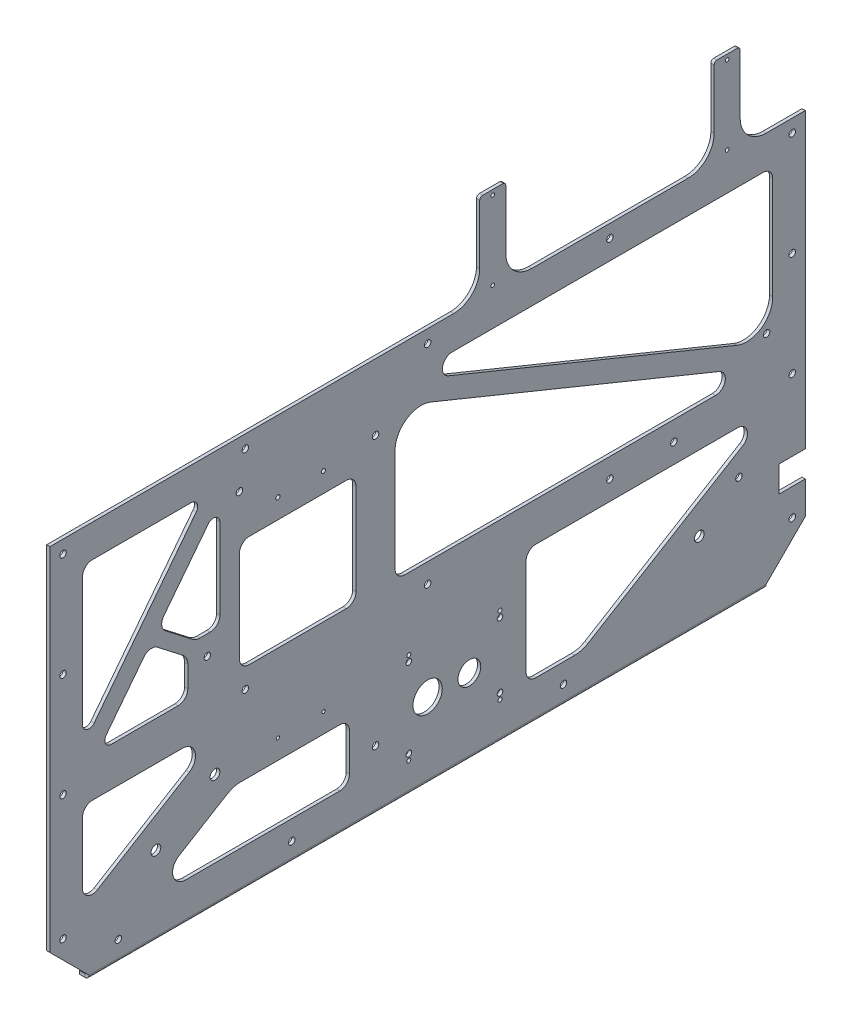
SolidWorks part; units mm, degrees
note: The reader was unsure of these and kept them because the rebuilt part matched: flange length of "Edge-Flange1".
material "6061-T6 (SS)"
ref_plane "Front Plane" through (0, 0, 0) normal (0, 0, 1) x (1, 0, 0)
ref_plane "Top Plane" through (0, 0, 0) normal (0, 1, 0) x (1, 0, 0)
ref_plane "Right Plane" through (0, 0, 0) normal (1, 0, 0) x (0, 0, -1)
sketch "Sketch1" plane through (0, 0, 0) normal (1, 0, 0) x (0, 0, -1)
  line L0 (330.2, 0) -> (-330.2, 0)
  line L1 (-330.2, 0) -> (-368.3, 38.1)
  line L2 (-368.3, 38.1) -> (-368.3, 381)
  line L3 (-368.3, 381) -> (368.3, 381)
  line L4 (368.3, 381) -> (368.3, 38.1)
  line L5 (368.3, 38.1) -> (330.2, 0)
  point P4 (0, 0)
  dimension "D1" = 736.6
  dimension "D2" = 381
  dimension "D3" = 38.1
  dimension "D4" = 45
base flange "Base-Flange1" sketch "Sketch1" thickness 3.175 reverse thickness direction no parameters "D1"=0.7366
sketch "Sketch11" plane through (0, 0, 0) normal (1, 0, 0) x (0, 0, -1)
  line L0 (304.8, 381) -> (304.8, 466.725)
  line L1 (304.8, 466.725) -> (279.4, 466.725)
  line L2 (279.4, 466.725) -> (279.4, 381)
  line L3 (368.3, 381) -> (-368.3, 381) construction
  line L4 (279.4, 381) -> (304.8, 381)
  line L5 (368.3, 381) -> (-368.3, 381) construction
  line L6 (368.3, 38.1) -> (368.3, 381) construction
  line L8 (76.2, 381) -> (50.8, 381)
  line L9 (76.2, 381) -> (76.2, 466.725)
  line L10 (76.2, 466.725) -> (50.8, 466.725)
  line L11 (50.8, 381) -> (50.8, 466.725)
  dimension "D1" = 25.4
  dimension "D2" = 85.725
  dimension "D3" = 63.5
  dimension "D4" = 228.6
base flange "Tab1" sketch "Sketch11" thickness 3.175 reverse thickness direction no parameters "D1"=0.7366
sketch "Sketch6" plane through (0, 0, 0) normal (1, 0, 0) x (0, 0, -1)
  circle A0 centre (264.9792, 73.025) radius 4.7625
  circle A1 centre (0, 69.85) radius 14.2875
  circle A2 centre (-264.9792, 73.025) radius 4.7625
  circle A3 centre (132.4896, 14.2875) radius 3.175 construction
  circle A4 centre (-132.4896, 14.2875) radius 3.175 construction
  circle A5 centre (132.4896, 14.2875) radius 3.175
  circle A6 centre (-132.4896, 14.2875) radius 3.175
  dimension "D1" = 28.575
  dimension "D2" = 9.525
  dimension "D3" = 9.525
extrude "Cut-Extrude1" cut sketch "Sketch6" against normal through all normal cut yes
sketch "Sketch7" plane through (0, 0, 0) normal (1, 0, 0) x (0, 0, -1)
  line L0 (368.3, 95.25) -> (368.3, 69.85)
  line L2 (368.3, 95.25) -> (342.9, 95.25)
  line L4 (368.3, 69.85) -> (342.9, 69.85)
  line L7 (342.9, 95.25) -> (342.9, 69.85)
  line L8 (349.2669, 95.25) -> (346.0496, 95.25) construction
  line L9 (342.9, 92.1004) -> (342.9, 88.8831) construction
  line L12 (279.4, 381) -> (76.2, 381) construction
  line L13 (-368.3, 381) -> (-368.3, 38.1) construction
  line L16 (-368.3, 368.3) -> (368.3, 368.3) construction
  line L17 (368.3, 38.1) -> (368.3, 381) construction
  line L18 (355.6, 368.3) -> (355.6, 165.1) construction
  line L19 (-355.6, 368.3) -> (-355.6, 165.1) construction
  circle A0 centre (-50.8, 53.975) radius 2.6035 construction
  circle A1 centre (-50.8, 53.975) radius 2.6035 construction
  circle A2 centre (-355.6, 43.3605) radius 3.175 construction
  circle A3 centre (-355.6, 165.1) radius 3.175 construction
  circle A4 centre (-177.8, 165.1) radius 3.175 construction
  circle A5 centre (0, 165.1) radius 3.175 construction
  circle A6 centre (177.8, 165.1) radius 3.175 construction
  circle A7 centre (355.6, 43.3605) radius 3.175 construction
  circle A8 centre (355.6, 165.1) radius 3.175 construction
  circle A9 centre (-355.6, 43.3605) radius 3.175
  circle A10 centre (-355.6, 165.1) radius 3.175
  circle A11 centre (-177.8, 165.1) radius 3.175
  circle A12 centre (0, 165.1) radius 3.175
  circle A13 centre (177.8, 165.1) radius 3.175
  circle A14 centre (355.6, 43.3605) radius 3.175
  circle A15 centre (355.6, 165.1) radius 3.175
  circle A16 centre (-146.05, 311.4675) radius 1.5875 construction
  circle A17 centre (-214.8334, 211.6192) radius 3.175
  circle A18 centre (-301.625, 15.875) radius 3.175 construction
  circle A19 centre (-301.625, 15.875) radius 3.175
  circle A20 centre (-146.05, 311.4675) radius 1.5875 construction
  circle A21 centre (-146.05, 311.4675) radius 2.032
  circle A22 centre (-101.6, 311.4675) radius 2.032
  circle A23 centre (-101.6, 311.4675) radius 1.5875 construction
  circle A24 centre (-101.6, 311.4675) radius 1.5875 construction
  circle A25 centre (303.625, 103.575) radius 3.175 construction
  circle A26 centre (240.125, 165.1) radius 3.175 construction
  circle A27 centre (330.6125, 211.525) radius 3.175 construction
  circle A28 centre (303.625, 103.575) radius 3.175
  circle A29 centre (-101.6, 108.2675) radius 1.5875 construction
  circle A30 centre (-146.05, 108.2675) radius 1.5875 construction
  circle A31 centre (-101.6, 108.2675) radius 1.5875
  circle A32 centre (-146.05, 108.2675) radius 1.5875
  circle A33 centre (-50.8, 316.23) radius 2.6035 construction
  circle A34 centre (-50.8, 316.23) radius 2.6035 construction
  circle A35 centre (240.125, 165.1) radius 3.175
  circle A36 centre (330.6125, 211.525) radius 3.175
  circle A47 centre (-355.6, 368.3) radius 3.175
  circle A48 centre (-177.8, 368.3) radius 3.175
  circle A49 centre (0, 368.3) radius 3.175
  circle A50 centre (177.8, 368.3) radius 3.175
  circle A51 centre (355.6, 368.3) radius 3.175
  circle A52 centre (-50.8, 316.23) radius 3.175
  circle A53 centre (-50.8, 53.975) radius 3.175
  circle A54 centre (-355.6, 266.7) radius 3.175
  circle A55 centre (355.6, 266.7) radius 3.175
  circle A56 centre (63.5, 461.9625) radius 1.3891 construction
  circle A57 centre (63.5, 385.7625) radius 1.3891 construction
  circle A58 centre (63.5, 461.9625) radius 1.3891 construction
  circle A59 centre (63.5, 385.7625) radius 1.3891 construction
  circle A60 centre (63.5, 461.9625) radius 1.7859
  circle A61 centre (63.5, 385.7625) radius 1.7859
  circle A62 centre (292.1, 461.9625) radius 1.3891 construction
  circle A63 centre (292.1, 385.7625) radius 1.3891 construction
  circle A64 centre (292.1, 461.9625) radius 1.3891 construction
  circle A65 centre (292.1, 385.7625) radius 1.3891 construction
  circle A66 centre (292.1, 461.9625) radius 1.7859
  circle A67 centre (292.1, 385.7625) radius 1.7859
  dimension "D6" = 6.35
  dimension "D7" = 4.064
  dimension "D2" = 6.35
  dimension "D11" = 6.35
  dimension "D12" = 6.35
  dimension "D13" = 3.5719
  dimension "D1" = 25.4
  dimension "D3" = 12.7
  dimension "D4" = 169.3808
  dimension "D5" = 153.4666
  dimension "D8" = 12.7
  dimension "D10" = 12.7
  dimension "D9" = 5
extrude "Cut-Extrude2" cut sketch "Sketch7" against normal through all normal cut yes
sketch "Sketch8" plane through (0, 0, 0) normal (1, 0, 0) x (0, 0, -1)
  circle A0 centre (70.5879, 38.1) radius 2.7261 construction
  circle A6 centre (-18.3121, 108.585) radius 2.7261 construction
  circle A7 centre (-18.3121, 31.115) radius 2.7261 construction
  circle A8 centre (70.5879, 38.1) radius 2.7261
  circle A9 centre (40.7162, 69.85) radius 11.1125 construction
  circle A10 centre (-18.3121, 108.585) radius 2.7261
  circle A11 centre (-18.3121, 31.115) radius 2.7261
  circle A12 centre (40.7162, 69.85) radius 11.1125
  circle A13 centre (70.5879, 101.6) radius 2.7261 construction
  circle A14 centre (70.5879, 101.6) radius 2.7261
  circle A15 centre (70.5879, 107.442) radius 1.9514 construction
  circle A16 centre (70.5879, 32.258) radius 1.9514 construction
  circle A17 centre (-18.3121, 25.273) radius 1.9514 construction
  circle A18 centre (-18.3121, 114.427) radius 1.9514 construction
  circle A19 centre (70.5879, 107.442) radius 1.9514
  circle A20 centre (70.5879, 32.258) radius 1.9514
  circle A21 centre (-18.3121, 25.273) radius 1.9514
  circle A22 centre (-18.3121, 114.427) radius 1.9514
extrude "Cut-Extrude3" cut sketch "Sketch8" against normal through all normal cut yes
sketch "Sketch9" plane through (0, 0, 0) normal (1, 0, 0) x (0, 0, -1)
  line L0 (-207.3469, 108.0375) -> (-232.6594, 28.575) construction
  line L1 (-493.8589, 28.575) -> (-213.6969, 28.575) construction
  line L2 (-493.8589, 28.575) -> (-493.8589, -31.75) construction
  line L3 (-493.8589, -31.75) -> (-213.6969, -31.75) construction
  line L4 (-213.6969, 28.575) -> (-213.6969, -31.75) construction
  line L5 (-410.4594, 28.575) -> (-207.3469, 108.0375) construction
  line L6 (-207.3469, 108.0375) -> (-286.8094, 133.35) construction
  line L7 (-347.1344, 388.112) -> (-286.8094, 388.112) construction
  line L8 (-347.1344, 388.112) -> (-347.1344, 107.95) construction
  line L9 (-347.1344, 107.95) -> (-286.8094, 107.95) construction
  line L10 (-286.8094, 388.112) -> (-286.8094, 107.95) construction
  line L11 (-286.8094, 311.15) -> (-207.3469, 108.0375) construction
  line L12 (-368.3, 299.4001) -> (-450.85, 299.4001) construction
  line L13 (-368.3, 381) -> (-368.3, 38.1) construction
  circle A0 centre (-207.3469, 108.0375) radius 4.7625
  circle A1 centre (0, 69.85) radius 101.6 construction
  circle A2 centre (-207.3469, 108.0375) radius 218.1031 construction
  point P8 (0, -31.75)
  point P22 (-425.45, 108.0375)
  dimension "D1" = 9.525
  dimension "D4" = 203.2
  dimension "D11" = 82.55
  dimension "D2" = 60.325
  dimension "D3" = 280.162
  dimension "D5" = 18.9625
  dimension "D6" = 177.8
  dimension "D7" = 139.7
  dimension "D8" = 25.4
  dimension "D9" = 177.8
  dimension "D10" = 6.35
  dimension "D12" = 25.4
extrude "Cut-Extrude4" cut sketch "Sketch9" against normal through all normal cut yes
sketch "Sketch10" plane through (0, 0, 0) normal (1, 0, 0) x (0, 0, -1)
  line L0 (-207.3469, 108.0375) -> (-183.5344, 84.225) construction
  line L1 (-207.3469, 108.0375) -> (-183.5344, 131.85) construction
  line L2 (-207.3469, 108.0375) -> (-312.821, 108.0375) construction
  line L3 (-207.3469, 108.0375) -> (-207.3469, 197.5591) construction
  circle A0 centre (-207.3469, 108.0375) radius 33.676 construction
  circle A1 centre (-183.5344, 335.05) radius 3.175
  dimension "D1" = 45
  dimension "D2" = 6.35
  dimension "D3" = 47.625
  dimension "D4" = 203.2
extrude "Cut-Extrude5" cut sketch "Sketch10" against normal through all normal cut yes
fillet "Fillet1" [suppressed] radius 1.5875
fillet "Fillet2" radius 2.794 4 edges at (-1.5875, 466.725, -279.4) (-1.5875, 466.725, -304.8) (-1.5875, 466.725, -76.2) (-1.5875, 466.725, -50.8)
fillet "Fillet3" radius 25.4 4 edges at (-1.5875, 381, -279.4) (-1.5875, 381, -76.2) (-1.5875, 381, -50.8) (-1.5875, 381, -304.8)
sketch "Sketch12" plane through (0, 0, 0) normal (1, 0, 0) x (0, 0, -1)
  line L0 (355.6, 165.1) -> (-355.6, 165.1) construction
  line L1 (23.9702, 349.25) -> (327.025, 349.25)
  line L2 (-79.375, 292.4175) -> (-174.0094, 292.4175)
  line L3 (336.55, 349.25) -> (336.55, 184.15) construction
  line L4 (336.55, 184.15) -> (-31.75, 184.15) construction
  line L5 (-31.75, 184.15) -> (-31.75, 349.25) construction
  line L6 (336.55, 339.725) -> (336.55, 239.5952)
  line L7 (-31.75, 349.25) -> (336.55, 349.25) construction
  line L8 (355.6, 368.3) -> (355.6, 165.1) construction
  line L9 (355.6, 368.3) -> (-355.6, 368.3) construction
  line L10 (-355.6, 368.3) -> (-355.6, 165.1) construction
  line L11 (280.8298, 184.15) -> (-22.225, 184.15)
  line L12 (-183.5344, 282.8925) -> (-183.5344, 193.675)
  line L13 (-69.85, 282.8925) -> (-69.85, 193.675)
  line L14 (-79.375, 184.15) -> (-174.0094, 184.15)
  line L15 (301.5471, 216.0804) -> (20.3691, 330.907)
  line L16 (3.2529, 317.3196) -> (284.4309, 202.493)
  line L17 (-31.75, 193.675) -> (-31.75, 293.8048)
  line L18 (329.3478, 184.15) -> (336.55, 201.7861) construction
  line L19 (-325.1809, 210.4894) -> (-225.5776, 339.0102)
  line L20 (-336.55, 349.25) -> (-202.5844, 349.25) construction
  line L21 (-336.55, 349.25) -> (-336.55, 184.15) construction
  line L22 (-336.55, 184.15) -> (-202.5844, 184.15) construction
  line L23 (-202.5844, 349.25) -> (-202.5844, 184.15) construction
  line L24 (-213.9535, 322.9106) -> (-257.34, 266.9278)
  line L25 (-230.5968, 349.25) -> (-327.025, 349.25)
  line L26 (-336.55, 339.725) -> (-336.55, 214.3792)
  line L27 (-202.5844, 319.0208) -> (-202.5844, 240.1942)
  line L28 (-212.1094, 230.6692) -> (-221.7586, 230.6692)
  line L29 (-233.8834, 214.4059) -> (-233.8834, 193.675)
  line L30 (-243.4084, 184.15) -> (-308.5376, 184.15)
  line L31 (-336.55, 195.8195) -> (-321.4926, 184.15) construction
  line L32 (-217.6418, 349.25) -> (-202.5844, 337.5805) construction
  line L33 (-238.8038, 224.4442) -> (-263.4257, 243.5261)
  line L34 (-229.5382, 233.3309) -> (-255.646, 253.5644)
  line L35 (-226.1038, 230.6692) -> (-233.8834, 220.6309) construction
  line L36 (-276.7891, 241.8321) -> (-313.5567, 194.3898)
  arc A0 (301.5471, 216.0804) -> (336.55, 239.5952) centre (311.15, 239.5952) ccw
  arc A1 (3.2529, 317.3196) -> (-31.75, 293.8048) centre (-6.35, 293.8048) ccw
  arc A2 (284.4309, 202.493) -> (280.8298, 184.15) centre (280.8298, 193.675) cw
  arc A3 (20.3691, 330.907) -> (23.9702, 349.25) centre (23.9702, 339.725) cw
  arc A4 (-255.646, 253.5644) -> (-257.34, 266.9278) centre (-249.8113, 261.0931) cw
  arc A5 (-263.4257, 243.5261) -> (-276.7891, 241.8321) centre (-269.2604, 235.9974) ccw
  arc A6 (-233.8834, 193.675) -> (-243.4084, 184.15) centre (-243.4084, 193.675) cw
  arc A7 (-202.5844, 240.1942) -> (-212.1094, 230.6692) centre (-212.1094, 240.1942) cw
  arc A8 (-327.025, 349.25) -> (-336.55, 339.725) centre (-327.025, 339.725) ccw
  arc A9 (327.025, 349.25) -> (336.55, 339.725) centre (327.025, 339.725) cw
  arc A10 (-22.225, 184.15) -> (-31.75, 193.675) centre (-22.225, 193.675) cw
  arc A11 (-183.5344, 193.675) -> (-174.0094, 184.15) centre (-174.0094, 193.675) ccw
  arc A12 (-69.85, 193.675) -> (-79.375, 184.15) centre (-79.375, 193.675) cw
  arc A13 (-69.85, 282.8925) -> (-79.375, 292.4175) centre (-79.375, 282.8925) ccw
  arc A14 (-174.0094, 292.4175) -> (-183.5344, 282.8925) centre (-174.0094, 282.8925) ccw
  arc A15 (-213.9535, 322.9106) -> (-202.5844, 319.0208) centre (-208.9344, 319.0208) cw
  arc A16 (-325.1809, 210.4894) -> (-336.55, 214.3792) centre (-330.2, 214.3792) cw
  arc A17 (-313.5567, 194.3898) -> (-308.5376, 184.15) centre (-308.5376, 190.5) ccw
  arc A18 (-225.5776, 339.0102) -> (-230.5968, 349.25) centre (-230.5968, 342.9) ccw
  arc A19 (-229.5382, 233.3309) -> (-221.7586, 230.6692) centre (-221.7586, 243.3692) ccw
  arc A20 (-238.8038, 224.4442) -> (-233.8834, 214.4059) centre (-246.5834, 214.4059) cw
  point P4 (-214.8334, 211.6192)
  point P7 (-50.8, 316.23)
  point P9 (-101.6, 311.4675)
  point P27 (-183.5344, 335.05)
  point P33 (-31.75, 331.6139)
  point P39 (-24.5478, 349.25)
  point P50 (-270.9544, 249.3608)
  point P53 (-233.8834, 184.15)
  point P56 (-202.5844, 230.6692)
  point P70 (-69.85, 184.15)
  dimension "D15" = 9.525
  dimension "D14" = 25.4
  dimension "D17" = 9.525
  dimension "D18" = 6.35
  dimension "D19" = 6.35
  dimension "D20" = 12.7
  dimension "D1" = 19.05
  dimension "D2" = 19.05
  dimension "D3" = 19.05
  dimension "D4" = 19.05
  dimension "D5" = 19.05
  dimension "D6" = 19.05
  dimension "D7" = 38.1
  dimension "D8" = 19.05
  dimension "D9" = 19.05
  dimension "D10" = 19.05
  dimension "D11" = 19.05
  dimension "D12" = 19.05
  dimension "D13" = 19.05
  dimension "D16" = 12.7
extrude "Cut-Extrude6" cut sketch "Sketch12" against normal through all normal cut yes
sketch "Sketch13" plane through (0, 0, 0) normal (1, 0, 0) x (0, 0, -1)
  line L0 (-355.6, 43.3605) -> (-355.6, 165.1) construction
  line L1 (-355.6, 165.1) -> (355.6, 165.1) construction
  line L2 (355.6, 165.1) -> (355.6, 43.3605) construction
  line L3 (336.55, 146.05) -> (95.9879, 146.05) construction
  line L4 (95.9879, 136.525) -> (95.9879, 42.8625)
  line L5 (150.3859, 33.3375) -> (336.55, 146.05) construction
  line L6 (105.5129, 33.3375) -> (143.2959, 33.3375)
  line L7 (105.5129, 146.05) -> (302.4269, 146.05)
  line L8 (307.36, 128.377) -> (156.451, 37.0096)
  line L9 (-85.725, 33.3375) -> (-236.0213, 33.3375)
  line L10 (-242.6153, 56.8915) -> (-195.4823, 85.5255)
  line L11 (-182.2944, 89.2175) -> (-85.725, 89.2175)
  line L12 (-76.2, 79.6925) -> (-76.2, 42.8625)
  line L13 (-232.4679, 122.496) -> (-322.0795, 68.0556)
  line L14 (-336.55, 76.1961) -> (-336.55, 136.525)
  line L15 (-327.025, 146.05) -> (-239.0619, 146.05)
  arc A0 (302.4269, 146.05) -> (307.36, 128.377) centre (302.4269, 136.525) cw
  arc A1 (-232.4679, 122.496) -> (-239.0619, 146.05) centre (-239.0619, 133.35) ccw
  arc A2 (-236.0213, 33.3375) -> (-242.6153, 56.8915) centre (-236.0213, 46.0375) cw
  arc A3 (105.5129, 146.05) -> (95.9879, 136.525) centre (105.5129, 136.525) ccw
  arc A4 (95.9879, 42.8625) -> (105.5129, 33.3375) centre (105.5129, 42.8625) ccw
  arc A5 (-85.725, 33.3375) -> (-76.2, 42.8625) centre (-85.725, 42.8625) ccw
  arc A6 (-85.725, 89.2175) -> (-76.2, 79.6925) centre (-85.725, 79.6925) cw
  arc A7 (-336.55, 136.525) -> (-327.025, 146.05) centre (-327.025, 136.525) cw
  arc A8 (156.451, 37.0096) -> (143.2959, 33.3375) centre (143.2959, 58.7375) cw
  arc A9 (-195.4823, 85.5255) -> (-182.2944, 89.2175) centre (-182.2944, 63.8175) cw
  arc A10 (-322.0795, 68.0556) -> (-336.55, 76.1961) centre (-327.025, 76.1961) cw
  point P10 (70.5879, 101.6)
  point P13 (264.9792, 73.025)
  point P14 (132.4896, 14.2875)
  point P27 (-50.8, 53.975)
  point P29 (-264.9792, 73.025)
  point P31 (-207.3469, 108.0375)
  point P33 (-146.05, 108.2675)
  point P45 (95.9879, 33.3375)
  dimension "D6" = 9.525
  dimension "D14" = 9.525
  dimension "D15" = 25.4
  dimension "D16" = 9.525
  dimension "D17" = 12.7
  dimension "D1" = 25.4
  dimension "D2" = 19.05
  dimension "D3" = 25.4
  dimension "D4" = 19.05
  dimension "D5" = 19.05
  dimension "D7" = 19.05
  dimension "D8" = 19.05
  dimension "D9" = 25.4
  dimension "D10" = 25.4
  dimension "D11" = 25.4
  dimension "D12" = 25.4
  dimension "D13" = 19.05
extrude "Cut-Extrude7" cut sketch "Sketch13" against normal through all normal cut yes
edge flange "Edge-Flange1" sketch "Sketch16" flange angle 90 flange length 9.525 flange position bend outside bend radius 0.7366 thickness 3.175 relief rectangular parameters "D6"=10
sketch "Sketch16" plane through (-3.175, 0, 0) normal (0, -1, 0) x (0, 0, 1)
  line L2 (-330.2, 0) -> (-330.2, 6.35)
  line L3 (-330.2, 6.35) -> (330.2, 6.35)
  line L4 (330.2, 6.35) -> (330.2, 0)
  line L5 (330.2, 0) -> (-330.2, 0) construction
  line L6 (330.2, 0) -> (-330.2, 0)
bend "EdgeBend1" bend radius 0.7366 bend angle 90 parameters "D5"=1
sketch "Bend-Lines1" [suppressed] plane through (0, 0, 0) normal (0, 1, 0) x (1, 0, 0)
sketch "Bounding-Box1" [suppressed] plane through (0, 0, 0) normal (0, 1, 0) x (1, 0, 0)
sheet metal parameters "Sheet-Metal1" thickness 3.175 parameters "D1"=0.7366
flat pattern "Flat-Pattern1" [suppressed]
sketch "Bend-Lines2" plane through (0, 0, 0) normal (0, 1, 0) x (1, 0, 0)
sketch3d "Bounding-Box2" [suppressed]
  line L0 (368.3, 0, 0) -> (-368.3, 0, 0) construction
  line L1 (368.3, 488.95, 0) -> (-368.3, 488.95, 0) construction
  line L2 (368.3, 0, 0) -> (368.3, 488.95, 0) construction
  line L3 (-368.3, 0, 0) -> (-368.3, 488.95, 0) construction
sheet metal parameters "Sheet-Metal2" thickness 3.175 parameters "D1"=0.7366
flat pattern "Flat-Pattern7"
sketch "Bend-Lines3" plane through (0, 0, 0) normal (0, 1, 0) x (1, 0, 0)
sketch3d "Bounding-Box3" [suppressed]
  line L0 (368.3, 0, 0) -> (-368.3, 0, 0) construction
  line L1 (368.3, 466.725, 0) -> (-368.3, 466.725, 0) construction
  line L2 (368.3, 0, 0) -> (368.3, 466.725, 0) construction
  line L3 (-368.3, 0, 0) -> (-368.3, 466.725, 0) construction
sheet metal parameters "Sheet-Metal3" thickness 3.175 parameters "D1"=0.7366
flat pattern "Flat-Pattern7"
sketch "Bend-Lines3" plane through (0, 0, 0) normal (0, 1, 0) x (1, 0, 0)
sketch3d "Bounding-Box3" [suppressed]
  line L0 (368.3, 0, 0) -> (-368.3, 0, 0) construction
  line L1 (368.3, 431.8, 0) -> (-368.3, 431.8, 0) construction
  line L2 (368.3, 0, 0) -> (368.3, 431.8, 0) construction
  line L3 (-368.3, 0, 0) -> (-368.3, 431.8, 0) construction
sheet metal parameters "Sheet-Metal4" thickness 3.175 parameters "D1"=0.7366
flat pattern "Flat-Pattern7"
sketch "Bend-Lines3" plane through (0, 0, 0) normal (0, 1, 0) x (1, 0, 0)
sketch3d "Bounding-Box3" [suppressed]
  line L0 (368.3, 0, 0) -> (-368.3, 0, 0) construction
  line L1 (368.3, 406.4, 0) -> (-368.3, 406.4, 0) construction
  line L2 (368.3, 0, 0) -> (368.3, 406.4, 0) construction
  line L3 (-368.3, 0, 0) -> (-368.3, 406.4, 0) construction
sheet metal parameters "Sheet-Metal5" thickness 3.175 parameters "D1"=0.7366
flat pattern "Flat-Pattern7"
sketch "Bend-Lines3" plane through (0, 0, 0) normal (0, 1, 0) x (1, 0, 0)
sketch3d "Bounding-Box3" [suppressed]
  line L0 (368.3, 0, 0) -> (-368.3, 0, 0) construction
  line L1 (368.3, 406.4, 0) -> (-368.3, 406.4, 0) construction
  line L2 (368.3, 0, 0) -> (368.3, 406.4, 0) construction
  line L3 (-368.3, 0, 0) -> (-368.3, 406.4, 0) construction
sheet metal parameters "Sheet-Metal6" thickness 3.175 parameters "D1"=0.7366
flat pattern "Flat-Pattern7"
sketch "Bend-Lines3" plane through (0, 0, 0) normal (0, 1, 0) x (1, 0, 0)
sketch3d "Bounding-Box3" [suppressed]
  line L0 (368.3, 0, 0) -> (-368.3, 0, 0) construction
  line L1 (368.3, 466.725, 0) -> (-368.3, 466.725, 0) construction
  line L2 (368.3, 0, 0) -> (368.3, 466.725, 0) construction
  line L3 (-368.3, 0, 0) -> (-368.3, 466.725, 0) construction
sheet metal parameters "Sheet-Metal7" thickness 3.175 parameters "D1"=0.7366
flat pattern "Flat-Pattern7"
sketch "Bend-Lines3" plane through (0, 0, 0) normal (0, 1, 0) x (1, 0, 0)
sketch3d "Bounding-Box3" [suppressed]
  line L0 (368.3, 0, 0) -> (-368.3, 0, 0) construction
  line L1 (368.3, 431.8, 0) -> (-368.3, 431.8, 0) construction
  line L2 (368.3, 0, 0) -> (368.3, 431.8, 0) construction
  line L3 (-368.3, 0, 0) -> (-368.3, 431.8, 0) construction
sheet metal parameters "Sheet-Metal8" thickness 3.175 parameters "D1"=0.7366
flat pattern "Flat-Pattern7"
sketch "Bend-Lines3" plane through (0, 0, 0) normal (0, 1, 0) x (1, 0, 0)
sketch3d "Bounding-Box3" [suppressed]
  line L0 (368.3, 0, 0) -> (-368.3, 0, 0) construction
  line L1 (368.3, 466.725, 0) -> (-368.3, 466.725, 0) construction
  line L2 (368.3, 0, 0) -> (368.3, 466.725, 0) construction
  line L3 (-368.3, 0, 0) -> (-368.3, 466.725, 0) construction
sheet metal parameters "Sheet-Metal10" thickness 3.175 parameters "D1"=0.7366
flat pattern "Flat-Pattern7"
sketch "Bend-Lines3" plane through (0, 0, 0) normal (0, 1, 0) x (1, 0, 0)
sketch3d "Bounding-Box3" [suppressed]
  line L0 (368.3, 0, 0) -> (-368.3, 0, 0) construction
  line L1 (368.3, 466.725, 0) -> (-368.3, 466.725, 0) construction
  line L2 (368.3, 0, 0) -> (368.3, 466.725, 0) construction
  line L3 (-368.3, 0, 0) -> (-368.3, 466.725, 0) construction
sheet metal parameters "Sheet-Metal11" thickness 3.175 parameters "D1"=0.7366
flat pattern "Flat-Pattern7"
sketch "Bend-Lines3" plane through (0, 0, 0) normal (1, 0, 0) x (0, 0, -1)
  line L0 (-330.2, -1.8253) -> (330.2, -1.8253) construction
  line L1 (-330.2, -1.8253) -> (330.2, -1.8253) construction
sketch3d "Bounding-Box3" [suppressed]
  line L0 (368.3, -9.2641, 0) -> (-368.3, -9.2641, 0) construction
  line L1 (368.3, 466.725, 0) -> (-368.3, 466.725, 0) construction
  line L2 (368.3, -9.2641, 0) -> (368.3, 466.725, 0) construction
  line L3 (-368.3, -9.2641, 0) -> (-368.3, 466.725, 0) construction
bend of the flat pattern "Flatten-<EdgeBend1>1"
